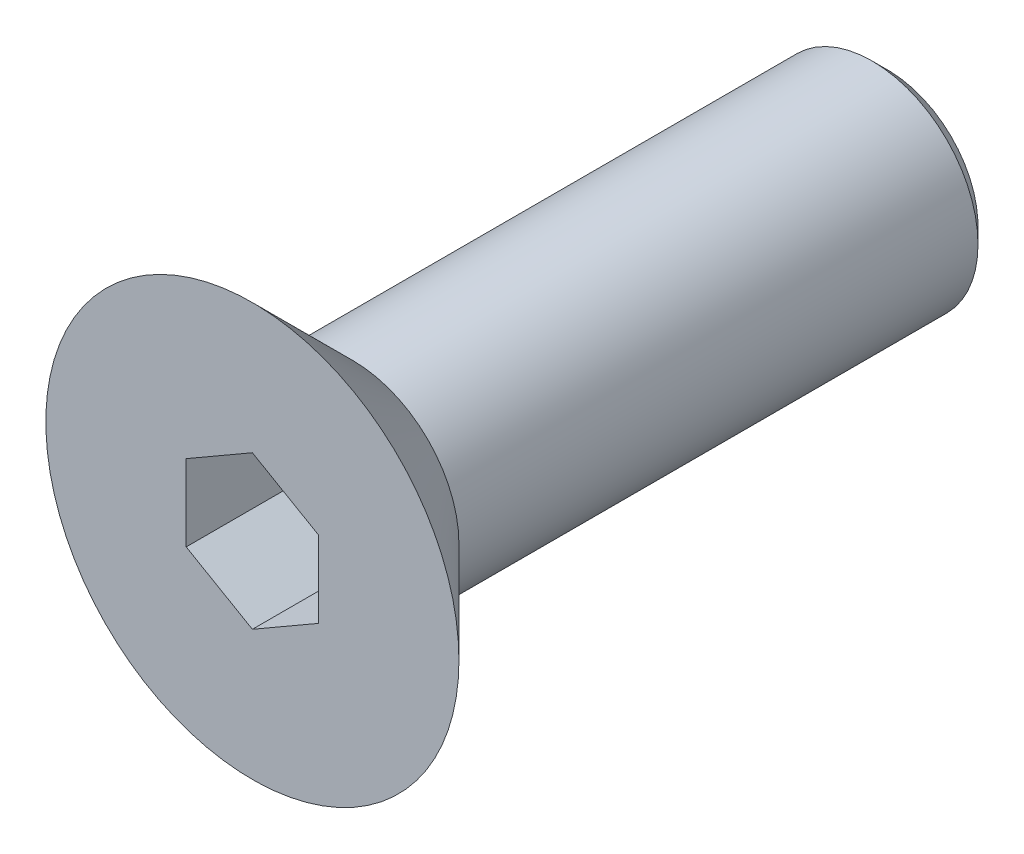
SolidWorks part; units mm, degrees
ref_plane "Front Plane" through (0, 0, 0) normal (0, 0, 1) x (1, 0, 0)
ref_plane "Top Plane" through (0, 0, 0) normal (0, 1, 0) x (1, 0, 0)
ref_plane "Right Plane" through (0, 0, 0) normal (1, 0, 0) x (0, 0, -1)
sketch "Sketch1" plane through (0, 0, 0) normal (0, 0, 1) x (1, 0, 0)
  circle A0 centre (0, 0) radius 4
  dimension "D1" = 8
extrude "Boss-Extrude1" add sketch "Sketch1" along normal blind 2.3
sketch "Sketch2" plane through (0, 0, 0) normal (0, 0, -1) x (-1, 0, 0)
  circle A0 centre (0, 0) radius 2
  dimension "D1" = 4
extrude "Boss-Extrude2" add sketch "Sketch2" along normal blind 9.7
chamfer "Chamfer1" distance 0.3 angle 45 1 edges at (-2, 0, -9.7)
sketch "Sketch3" plane through (0, 0, 2.3) normal (0, 0, 1) x (1, 0, 0)
  line L1 (0, 1.4434) -> (-1.25, 0.7217)
  line L2 (-1.25, 0.7217) -> (-1.25, -0.7217)
  line L3 (-1.25, -0.7217) -> (0, -1.4434)
  line L4 (0, -1.4434) -> (1.25, -0.7217)
  line L5 (1.25, -0.7217) -> (1.25, 0.7217)
  line L6 (1.25, 0.7217) -> (0, 1.4434)
  circle A0 centre (0, 0) radius 1.25 construction
  dimension "D1" = 2.5
extrude "Cut-Extrude1" cut sketch "Sketch3" against normal blind 2
chamfer "Chamfer2" distance 2.4 angle 45 1 edges at (4, 0, 0)
